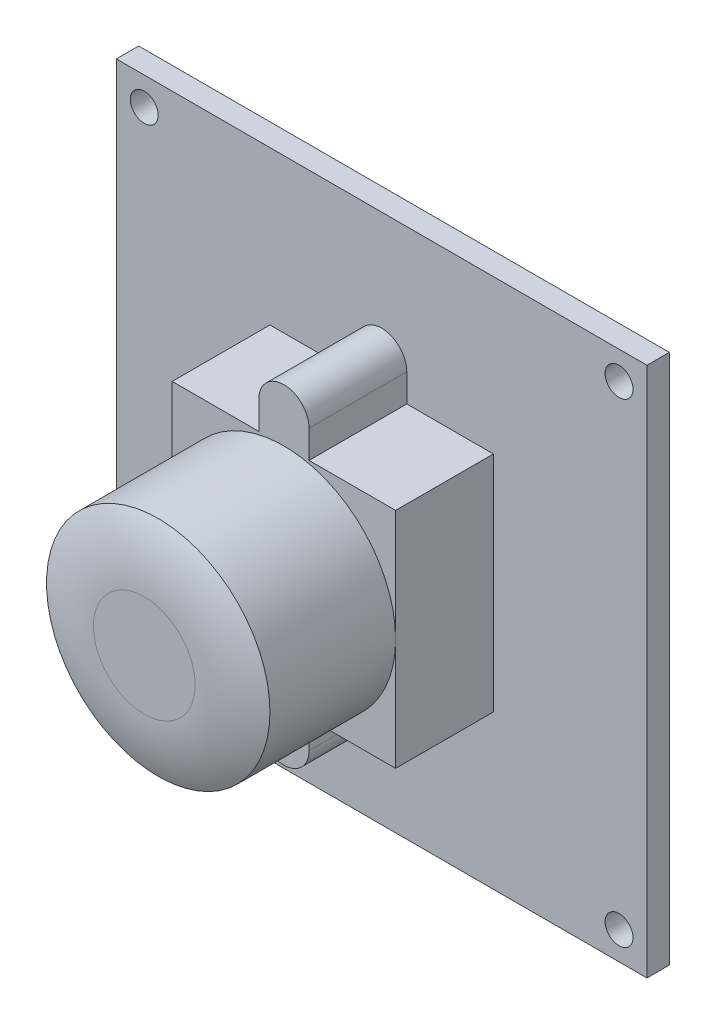
SolidWorks part; units mm, degrees
ref_plane "Plan de face" through (0, 0, 0) normal (0, 0, 1) x (1, 0, 0)
ref_plane "Plan de dessus" through (0, 0, 0) normal (0, 1, 0) x (1, 0, 0)
ref_plane "Plan de droite" through (0, 0, 0) normal (1, 0, 0) x (0, 0, -1)
sketch "Esquisse1" plane through (0, 0, 0) normal (0, 0, 1) x (1, 0, 0)
  line L0 (19, 38) -> (19, 0) construction
  line L1 (0, 0) -> (38, 0)
  line L2 (0, 0) -> (0, 38)
  line L3 (0, 38) -> (38, 38)
  line L4 (38, 0) -> (38, 38)
  circle A0 centre (2, 36) radius 1
  circle A1 centre (2, 2) radius 1
  circle A2 centre (36, 2) radius 1
  circle A3 centre (36, 36) radius 1
  dimension "D7" = 2
  dimension "D1" = 38
  dimension "D2" = 38
  dimension "D3" = 2
  dimension "D4" = 2
  dimension "D5" = 2
  dimension "D6" = 2
extrude "Boss.-Extru.1" add sketch "Esquisse1" along normal blind 1.6
sketch "Esquisse2" plane through (0, 0, 1.6) normal (0, 0, 1) x (1, 0, 0)
  line L0 (19, 38) -> (19, 0) construction
  line L1 (38, 38) -> (0, 38) construction
  line L2 (0, 0) -> (38, 0) construction
  line L3 (38, 19) -> (0, 19) construction
  line L4 (38, 0) -> (38, 38) construction
  line L5 (0, 38) -> (0, 0) construction
  line L6 (11, 27) -> (17.2, 27)
  line L7 (11, 27) -> (27, 27) construction
  line L8 (11, 27) -> (11, 11)
  line L9 (11, 11) -> (27, 11) construction
  line L10 (27, 27) -> (27, 11)
  line L11 (17.2, 27) -> (17.2, 29)
  line L12 (17.2, 29) -> (20.8, 29) construction
  line L13 (20.8, 29) -> (20.8, 27)
  line L14 (20.8, 27) -> (27, 27)
  line L15 (20.8, 11) -> (27, 11)
  line L16 (20.8, 9) -> (20.8, 11)
  line L17 (17.2, 11) -> (17.2, 9)
  line L18 (11, 11) -> (17.2, 11)
  arc A0 (17.2, 29) -> (20.8, 29) centre (19, 29) cw
  arc A1 (17.2, 9) -> (20.8, 9) centre (19, 9) ccw
  dimension "D2" = 3.6
  dimension "D1" = 16
  dimension "D3" = 2
extrude "Boss.-Extru.2" add sketch "Esquisse2" along normal blind 7
sketch "Esquisse3" plane through (0, 0, 8.6) normal (0, 0, 1) x (1, 0, 0)
  line L0 (19, 30.8) -> (19, 7.2) construction
  line L1 (27, 19) -> (11, 19) construction
  line L2 (27, 11) -> (27, 27) construction
  line L3 (11, 27) -> (11, 11) construction
  arc A0 (20.8, 29) -> (17.2, 29) centre (19, 29) ccw construction
  arc A1 (17.2, 9) -> (20.8, 9) centre (19, 9) ccw construction
  circle A2 centre (19, 19) radius 8
  dimension "D1" = 16
extrude "Boss.-Extru.3" add sketch "Esquisse3" along normal blind 10
chamfer "Chanfrein1" distance 1 angle 60 1 edges at (27, 19, 18.6) first distance on face at (27, 19, 18.6)
fillet "Congé1" radius 10 1 edges at (25.2679, 19, 18.6)
sketch "Esquisse4" plane through (0, 0, 0) normal (0, 0, -1) x (-1, 0, 0)
  line L0 (0, 38) -> (0, 0) construction
  line L1 (0, 11) -> (-6, 11)
  line L2 (0, 11) -> (0, 21)
  line L3 (0, 21) -> (-6, 21)
  line L4 (-6, 11) -> (-6, 21)
  line L5 (0, 0) -> (-38, 0) construction
  dimension "D1" = 11
  dimension "D2" = 10
  dimension "D3" = 6
extrude "Boss.-Extru.4" add sketch "Esquisse4" along normal blind 14
